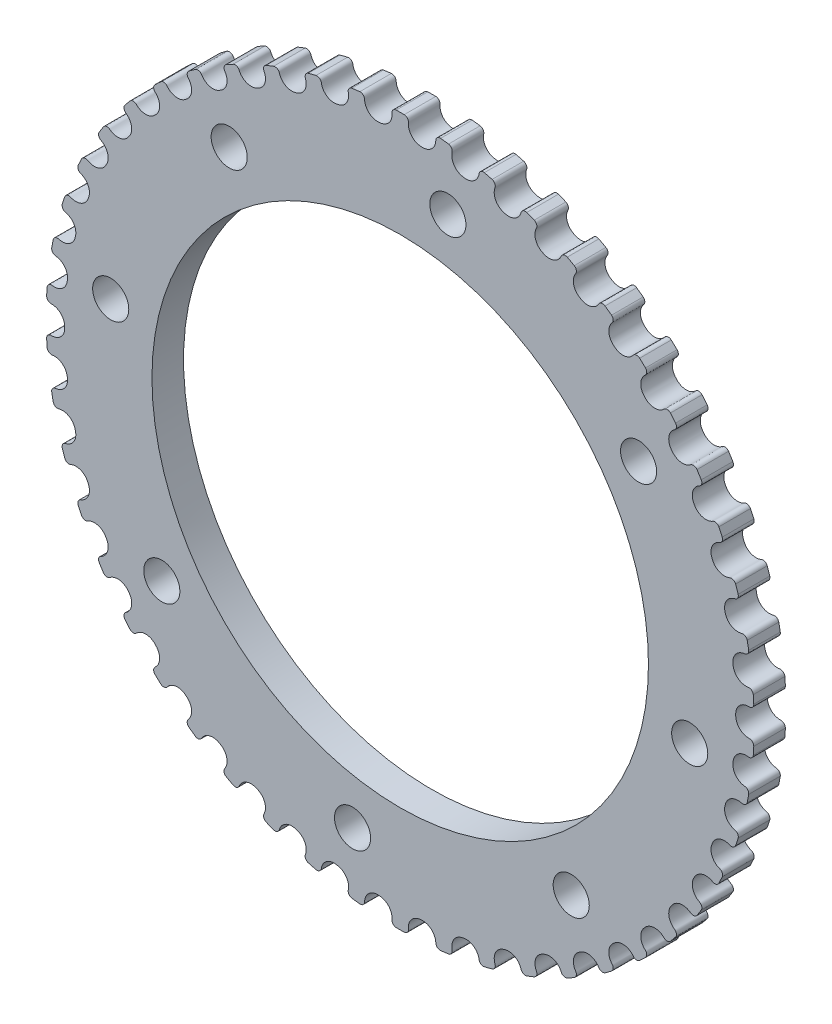
SolidWorks part; units mm, degrees
material "Thornel Mat VMA"
ref_plane "Front Plane" through (0, 0, 0) normal (0, 0, 1) x (1, 0, 0)
ref_plane "Top Plane" through (0, 0, 0) normal (0, 1, 0) x (1, 0, 0)
ref_plane "Right Plane" through (0, 0, 0) normal (1, 0, 0) x (0, 0, -1)
ref_axis "Axis1" through (0, 0, 55) along (0, 0, -1)
sketch "SketchRevolveGearBelt01" plane through (0, 0, 0) normal (1, 0, 0) x (0, 0, -1)
  line L0 (0, 0) -> (1, 0) construction
  line L1 (1.75, 0) -> (1.75, 39.2172)
  line L2 (1.75, 39.2172) -> (-1.75, 39.2172)
  line L3 (-1.75, 39.2172) -> (-1.75, 0)
  line L4 (-1.75, 0) -> (1.75, 0)
  dimension "GearBeltSide1" = 1.75
  dimension "GearBeltOutsideDiameter" = 39.2172
  dimension "GearBeltSide2" = 1.75
revolve "GearBelt01" add sketch "SketchRevolveGearBelt01" angle 360 about L0
sketch "SketchToothGearBelt01" plane through (0, 0, 0) normal (0, 0, 1) x (1, 0, 0)
  arc A0 (39.1647, 2.0323) -> (39.1647, -2.0323) centre (0, 0) cw
  spline S0 degree 3 poles (39.1647, -2.0323) (39.166, -2.006) (39.1649, -1.9663) (39.1569, -1.9141) (39.1478, -1.8755) (39.1356, -1.8378) (39.1204, -1.8013) (39.1023, -1.7661) (39.0814, -1.7324) (39.0578, -1.7006) (39.0317, -1.6708) (39.0033, -1.6432) (38.9728, -1.618) (38.9403, -1.5953) (38.9061, -1.5754) (38.8703, -1.5582) (38.8333, -1.5441) (38.7953, -1.533) (38.7565, -1.525) (38.7172, -1.5201) (38.6658, -1.5185) (38.59, -1.5198) (38.4897, -1.516) (38.3775, -1.5026) (38.2667, -1.4805) (38.158, -1.4498) (38.052, -1.4107) (37.9494, -1.3633) (37.8509, -1.3081) (37.7569, -1.2453) (37.6682, -1.1753) (37.5853, -1.0986) (37.5086, -1.0156) (37.4387, -0.9268) (37.376, -0.8329) (37.3208, -0.7343) (37.2735, -0.6317) (37.2344, -0.5257) (37.2037, -0.4169) (37.1817, -0.3061) (37.1683, -0.1939) (37.1652, -0.1051) (37.1655, -0.0405) (37.1655, 0) (37.1655, 0.0405) (37.1652, 0.1051) (37.1683, 0.1939) (37.1817, 0.3061) (37.2037, 0.4169) (37.2344, 0.5257) (37.2735, 0.6317) (37.3208, 0.7343) (37.376, 0.8329) (37.4387, 0.9268) (37.5086, 1.0156) (37.5853, 1.0986) (37.6682, 1.1753) (37.7569, 1.2453) (37.8509, 1.3081) (37.9494, 1.3633) (38.052, 1.4107) (38.158, 1.4498) (38.2667, 1.4805) (38.3775, 1.5026) (38.4897, 1.516) (38.59, 1.5198) (38.6658, 1.5185) (38.7172, 1.5201) (38.7565, 1.525) (38.7953, 1.533) (38.8333, 1.5441) (38.8703, 1.5582) (38.9061, 1.5754) (38.9403, 1.5953) (38.9728, 1.618) (39.0033, 1.6432) (39.0317, 1.6708) (39.0578, 1.7006) (39.0814, 1.7324) (39.1023, 1.7661) (39.1204, 1.8013) (39.1356, 1.8378) (39.1478, 1.8755) (39.1569, 1.9141) (39.1649, 1.9663) (39.166, 2.006) (39.1647, 2.0323) knots 0 0 0 0 0.012346 0.01852 0.024693 0.030866 0.037039 0.043212 0.049386 0.055559 0.061732 0.067905 0.074078 0.080252 0.086425 0.092598 0.098771 0.104944 0.111118 0.117291 0.123464 0.135171 0.152781 0.17039 0.188 0.205609 0.223219 0.240828 0.258438 0.276048 0.293657 0.311267 0.328876 0.346486 0.364095 0.381705 0.399315 0.416924 0.434534 0.452143 0.469753 0.487362 0.493681 0.5 0.506319 0.512638 0.530247 0.547857 0.565466 0.583076 0.600685 0.618295 0.635905 0.653514 0.671124 0.688733 0.706343 0.723952 0.741562 0.759172 0.776781 0.794391 0.812 0.82961 0.847219 0.864829 0.876536 0.882709 0.888882 0.895056 0.901229 0.907402 0.913575 0.919748 0.925922 0.932095 0.938268 0.944441 0.950614 0.956788 0.962961 0.969134 0.975307 0.98148 0.987654 1 1 1 1
extrude "ToothExtrudeCutGearBelt01" cut sketch "SketchToothGearBelt01" against normal blind 7.239 and the other way blind 7.239
pattern_circular "PatternGearBelt01" count 50 every 7.2 about axis through (0, 0, 55) along (0, 0, -1) of "ToothExtrudeCutGearBelt01"
sketch "BoreRevolveSketch" plane through (0, 0, 0) normal (1, 0, 0) x (0, 0, -1)
  line L0 (0, 0) -> (1, 0) construction
  line L1 (-7.239, 0) -> (7.239, 0)
  line L2 (7.239, 0) -> (7.239, 27.5)
  line L3 (7.239, 27.5) -> (-7.239, 27.5)
  line L4 (-7.239, 27.5) -> (-7.239, 0)
  dimension "BoreSide1" = 7.239
  dimension "TaperSide1" = 27.5
  dimension "BoreSide2" = 7.239
  dimension "TaperSide2" = 27.5
revolve "BoreRevolveCut" cut sketch "BoreRevolveSketch" angle 360 about L0
sketch "AuxiliarySketchGearBelt01" plane through (0, 0, 0) normal (0, 0, 1) x (1, 0, 0)
  circle A0 centre (0, 0) radius 39.7887 construction
  dimension "PitchDiameter" = 79.5774
sketch "Sketch1" plane through (0, 0, 1.75) normal (0, 0, 1) x (1, 0, 0)
  circle A0 centre (5.2787, 32.0684) radius 2 construction
  circle A1 centre (26.4084, 18.9432) radius 2 construction
  circle A2 centre (32.0684, -5.2787) radius 2 construction
  circle A3 centre (18.9432, -26.4084) radius 2 construction
  circle A4 centre (-5.2787, -32.0684) radius 2 construction
  circle A5 centre (-26.4084, -18.9432) radius 2 construction
  circle A6 centre (-32.0684, 5.2787) radius 2 construction
  circle A7 centre (-18.9432, 26.4084) radius 2 construction
  circle A8 centre (5.2787, 32.0684) radius 2
  circle A9 centre (26.4084, 18.9432) radius 2
  circle A10 centre (32.0684, -5.2787) radius 2
  circle A11 centre (18.9432, -26.4084) radius 2
  circle A12 centre (-5.2787, -32.0684) radius 2
  circle A13 centre (-26.4084, -18.9432) radius 2
  circle A14 centre (-32.0684, 5.2787) radius 2
  circle A15 centre (-18.9432, 26.4084) radius 2
extrude "Cut-Extrude1" cut sketch "Sketch1" against normal blind 10
